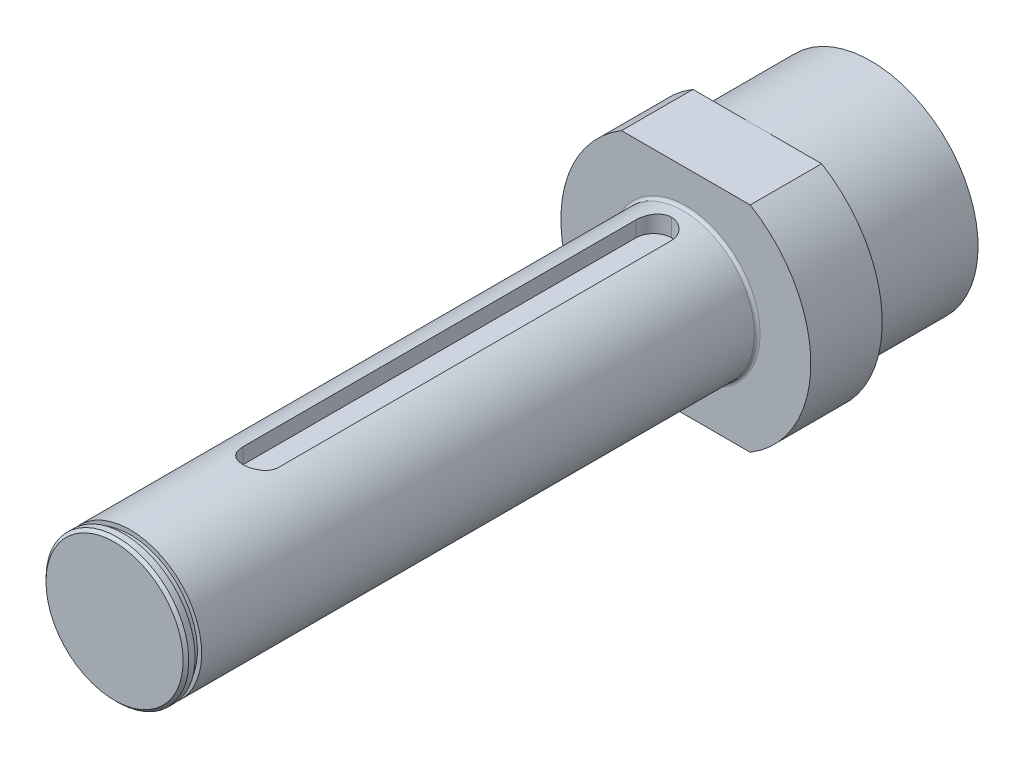
SolidWorks part; units mm, degrees
material "AISI 4130 Steel, normalized at 870C"
ref_plane "Front Plane" through (0, 0, 0) normal (0, 0, 1) x (1, 0, 0)
ref_plane "Top Plane" through (0, 0, 0) normal (0, 1, 0) x (1, 0, 0)
ref_plane "Right Plane" through (0, 0, 0) normal (1, 0, 0) x (0, 0, -1)
sketch "Sketch1" plane through (0, 0, 0) normal (0, 0, 1) x (1, 0, 0)
  circle A0 centre (0, 0) radius 13.9954
  circle A1 centre (0, 0) radius 19.05
  dimension "D1" = 27.9908
  dimension "D2" = 38.1
extrude "Boss-Extrude1" add sketch "Sketch1" along normal blind 63.5
sketch "Sketch2" plane through (0, 0, 63.5) normal (0, 0, 1) x (1, 0, 0)
  circle A0 centre (0, 0) radius 19.05
extrude "Boss-Extrude2" add sketch "Sketch2" along normal blind 12.7
sketch "Sketch3" plane through (0, 0, 76.2) normal (0, 0, 1) x (1, 0, 0)
  circle A0 centre (0, 0) radius 12.7
  dimension "D1" = 25.4
extrude "Boss-Extrude3" add sketch "Sketch3" along normal blind 127
fillet "Fillet1" radius 0.508 1 edges at (12.7, 0, 76.2)
chamfer "Chamfer1" distance 1.27 angle 45 1 edges at (12.7, 0, 203.2)
ref_plane "Plane1" through (0, 0, 78.74) normal (0, 0, 1) x (1, 0, 0)
sketch "Sketch4" plane through (0, 0, 78.74) normal (0, 0, 1) x (1, 0, 0)
  line L1 (3.175, 9.525) -> (-3.175, 9.525)
  line L2 (3.175, 9.525) -> (3.175, 15.875)
  line L3 (3.175, 15.875) -> (-3.175, 15.875)
  line L4 (-3.175, 9.525) -> (-3.175, 15.875)
  line L5 (3.175, 9.525) -> (-3.175, 15.875) construction
  line L6 (3.175, 15.875) -> (-3.175, 9.525) construction
  circle A0 centre (0, 0) radius 12.7
  point P3 (0, 12.7)
  dimension "D1" = 6.35
  dimension "D2" = 6.35
extrude "Cut-Extrude1" cut sketch "Sketch4" along normal blind 76.2 contours L2 A0 L4 L1 | A0 L2 L3 L4 region at (0, 11.0481, 78.74) region at (0, 14.2185, 78.74)
fillet "Fillet2" radius 3.175 4 edges at (3.175, 10.9109, 154.94) (-3.175, 10.9109, 154.94) (3.175, 10.9109, 78.74) (-3.175, 10.9109, 78.74)
sketch "Sketch5" plane through (0, 0, 0) normal (0, 0, -1) x (-1, 0, 0)
  line L0 (0, 0) -> (0, 19.05) construction
  line L1 (-24.3176, 19.05) -> (24.3176, 19.05)
  line L2 (0, 0) -> (7.7337, 0) construction
  line L3 (-24.3176, -19.05) -> (24.3176, -19.05)
  circle A0 centre (0, 0) radius 22.225
  circle A1 centre (0, 0) radius 19.05 construction
  circle M2 centre (0, 0) radius 19.05
  dimension "D1" = 44.45
extrude "Boss-Extrude4" add sketch "Sketch5" against normal up to surface (76.2 mm away) contours L1 A0 L3 M2 | L3 A0 L1 M2 region at (5.7238, 18.6089, 0) region at (-5.7238, 18.6089, 0) up to face at (13.208, 0, 76.2)
sketch "Sketch6" plane through (0, 0, 63.5) normal (0, 0, -1) x (-1, 0, 0)
  circle A1 centre (0, 0) radius 13.9954
  circle A2 centre (0, 0) radius 13.9954
  dimension "D1" = 0
extrude "Boss-Extrude5" add sketch "Sketch6" along normal up to surface (63.5 mm away) up to face at (0, 0, 0)
sketch "Sketch7" plane through (0, 0, 0) normal (0, 0, -1) x (-1, 0, 0)
  circle A0 centre (0, 0) radius 12.7
  circle A1 centre (0, 0) radius 25.2194
  dimension "D1" = 25.4
extrude "Cut-Extrude2" cut sketch "Sketch7" against normal blind 63.5
sketch "Sketch8" plane through (0, 0, 0) normal (0, 0, -1) x (-1, 0, 0)
  circle A0 centre (0, 0) radius 14.2875
  dimension "D1" = 28.575
extrude "Cut-Extrude3" cut sketch "Sketch8" against normal blind 19.05
sketch "Sketch9" plane through (0, 9.525, 0) normal (0, 1, 0) x (1, 0, 0)
  line L0 (-3.175, -81.915) -> (-3.175, -19.05) construction
  line L1 (12.7, -19.05) -> (-12.7, -19.05) construction
  line L2 (3.175, -81.915) -> (3.175, -19.05) construction
  line L3 (-3.175, -60.325) -> (3.175, -60.325) construction
  line L4 (-3.175, -63.5) -> (3.175, -63.5) construction
  line L5 (-11.4476, -63.5) -> (11.4476, -63.5) construction
  line L7 (-3.175, -60.325) -> (3.175, -60.325)
  line L8 (-3.175, -60.325) -> (-3.175, -19.05)
  line L9 (-3.175, -19.05) -> (3.175, -19.05)
  line L10 (3.175, -60.325) -> (3.175, -19.05)
  dimension "D1" = 3.175
extrude "Cut-Extrude4" cut sketch "Sketch9" along normal blind 25.4
fillet "Fillet3" radius 3.175 2 edges at (-3.175, 10.9109, 60.325) (3.175, 10.9109, 60.325)
sketch "Sketch10" plane through (0, 0, 19.05) normal (0, 0, -1) x (-1, 0, 0)
  circle A0 centre (0, 0) radius 33.9572
extrude "Cut-Extrude5" cut sketch "Sketch10" against normal up to surface (44.45 mm away) up to face at (0, 0, 63.5)
sketch "Sketch11" plane through (0, 0, 63.5) normal (0, 0, -1) x (-1, 0, 0)
  circle A0 centre (0, 0) radius 14.986
  circle A1 centre (0, 0) radius 19.05
  dimension "D1" = 29.972
  dimension "D2" = 38.1
extrude "Boss-Extrude6" add sketch "Sketch11" along normal blind 20.2184
sketch "Sketch12" plane through (0, 0, 203.2) normal (0, 0, 1) x (1, 0, 0)
  circle A0 centre (0, 0) radius 18.4868
extrude "Cut-Extrude6" cut sketch "Sketch12" against normal blind 25.4
ref_plane "Plane2" through (0, 0, 175.006) normal (0, 0, 1) x (1, 0, 0)
sketch "Sketch13" plane through (0, 0, 175.006) normal (0, 0, 1) x (1, 0, 0)
  circle A0 centre (0, 0) radius 11.938
  circle A1 centre (0, 0) radius 16.9385
  dimension "D1" = 23.876
extrude "Cut-Extrude7" cut sketch "Sketch13" along normal blind 1.1684
chamfer "Chamfer3" distance 0.508 angle 45 1 edges at (12.7, 0, 177.8)
ref_axis "Axis1" through (0, 0, 175.006) along (0, 0, -1)
